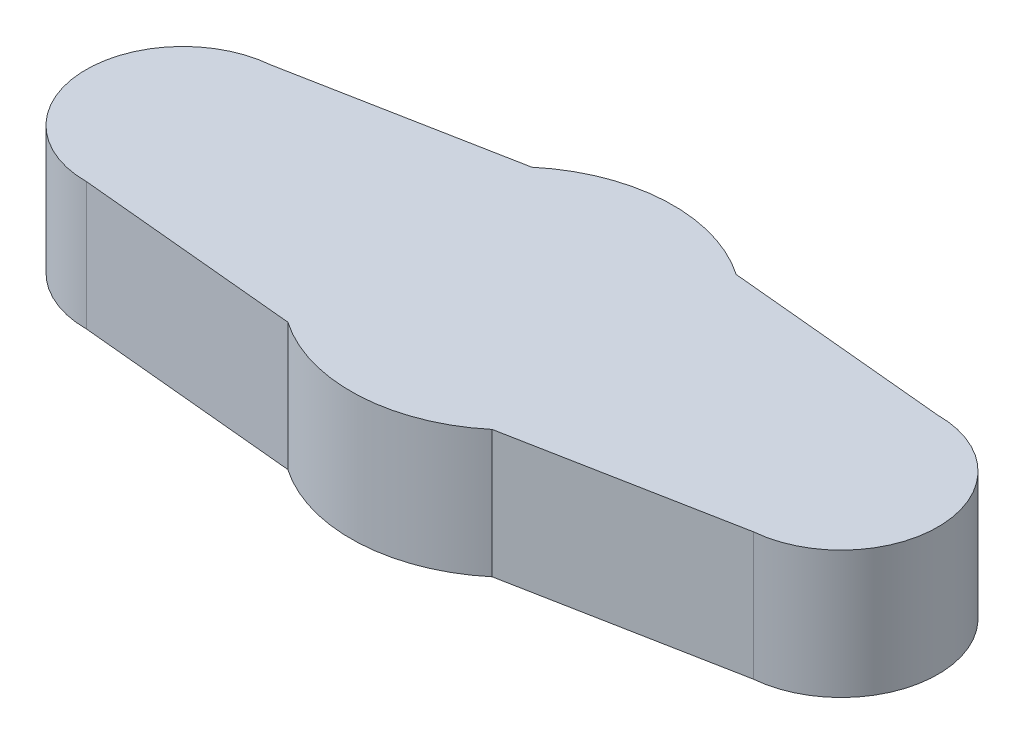
SolidWorks part; units mm, degrees
ref_plane "Front Plane" through (0, 0, 0) normal (0, 0, 1) x (1, 0, 0)
ref_plane "Top Plane" through (0, 0, 0) normal (0, 1, 0) x (1, 0, 0)
ref_plane "Right Plane" through (0, 0, 0) normal (1, 0, 0) x (0, 0, -1)
sketch "Sketch1" plane through (0, 19.05, 0) normal (0, 1, 0) x (1, 0, 0)
  line L8 (7.1827, 4.1213) -> (-5.1818, 1.7547)
  line L9 (-4.9411, -3.3196) -> (7.592, -4.505)
  line L10 (15.6773, -4.1213) -> (28.0418, -1.7547)
  line L11 (27.8011, 3.3196) -> (15.268, 4.505)
  line L12 (7.1827, 4.1213) -> (-5.1818, 1.7547)
  line L13 (-4.9411, -3.3196) -> (7.592, -4.505)
  line L14 (15.6773, -4.1213) -> (28.0418, -1.7547)
  line L15 (27.8011, 3.3196) -> (15.268, 4.505)
  line L20 (27.8917, 5.8624) -> (16.2283, 6.9655)
  line L21 (16.8662, -6.4799) -> (28.3728, -4.2775)
  line L22 (-5.0317, -5.8624) -> (6.6317, -6.9655)
  line L23 (5.9938, 6.4799) -> (-5.5128, 4.2775)
  line L24 (27.8917, 5.8624) -> (16.2283, 6.9655)
  line L25 (16.8662, -6.4799) -> (28.3728, -4.2775)
  line L26 (-5.0317, -5.8624) -> (6.6317, -6.9655)
  line L27 (5.9938, 6.4799) -> (-5.5128, 4.2775)
  circle A0 centre (11.43, 0) radius 2.032
  arc A9 (15.268, 4.505) -> (7.1827, 4.1213) centre (11.43, 0) ccw
  arc A10 (-5.1818, 1.7547) -> (-4.9411, -3.3196) centre (-5.0614, -0.7825) ccw
  arc A11 (7.592, -4.505) -> (15.6773, -4.1213) centre (11.43, 0) ccw
  arc A12 (28.0418, -1.7547) -> (27.8011, 3.3196) centre (27.9214, 0.7825) ccw
  arc A13 (15.268, 4.505) -> (7.1827, 4.1213) centre (11.43, 0) ccw
  arc A14 (-5.1818, 1.7547) -> (-4.9411, -3.3196) centre (-5.0614, -0.7825) ccw
  arc A15 (7.592, -4.505) -> (15.6773, -4.1213) centre (11.43, 0) ccw
  arc A16 (28.0418, -1.7547) -> (27.8011, 3.3196) centre (27.9214, 0.7825) ccw
  arc A21 (16.2283, 6.9655) -> (5.9938, 6.4799) centre (11.43, 0) ccw
  arc A22 (28.3728, -4.2775) -> (27.8917, 5.8624) centre (27.9214, 0.7825) ccw
  arc A23 (6.6317, -6.9655) -> (16.8662, -6.4799) centre (11.43, 0) ccw
  arc A24 (-5.5128, 4.2775) -> (-5.0317, -5.8624) centre (-5.0614, -0.7825) ccw
  arc A25 (16.2283, 6.9655) -> (5.9938, 6.4799) centre (11.43, 0) ccw
  arc A26 (28.3728, -4.2775) -> (27.8917, 5.8624) centre (27.9214, 0.7825) ccw
  arc A27 (6.6317, -6.9655) -> (16.8662, -6.4799) centre (11.43, 0) ccw
  arc A28 (-5.5128, 4.2775) -> (-5.0317, -5.8624) centre (-5.0614, -0.7825) ccw
  point P3 (0, 0)
  arc M2 (15.268, 4.505) -> (7.1827, 4.1213) centre (11.43, 0) ccw
  line M3 (7.1827, 4.1213) -> (-5.1818, 1.7547)
  arc M4 (-5.1818, 1.7547) -> (-4.9411, -3.3196) centre (-5.0614, -0.7825) ccw
  line M5 (-4.9411, -3.3196) -> (7.592, -4.505)
  arc M6 (7.592, -4.505) -> (15.6773, -4.1213) centre (11.43, 0) ccw
  line M7 (15.6773, -4.1213) -> (28.0418, -1.7547)
  arc M8 (28.0418, -1.7547) -> (27.8011, 3.3196) centre (27.9214, 0.7825) ccw
  line M9 (27.8011, 3.3196) -> (15.268, 4.505)
  dimension "D1" = 4.064
  dimension "D2" = 0
  dimension "D3" = 2.54
extrude "Boss-Extrude1" add sketch "Sketch1" along normal blind 2.159 contours L27 A28 L26 A27 L25 A26 L24 A25 A16 L14 A15 L13 A14 L12 A13 L15 | A0 M9 M2 M3 M4 M5 M6 M7 M8 | L14 A16 L15 A13 L12 A14 L13 A15 M2 M9 M8 M7 M6 M5 M4 M3 region at (11.1684, 19.05, -5.5134) region at (32.5329, 19.05, -1.0013)
extrude "Boss-Extrude2" add sketch "Sketch1<3>" against normal up to surface (2.54 mm away) contours L27 A28 L26 A27 L25 A26 L24 A25 A16 L14 A15 L13 A14 L12 A13 L15 region at (32.5329, 19.05, -1.0013)
sketch "Sketch1<3>" plane through (0, 19.05, 0) normal (0, 1, 0) x (1, 0, 0) same geometry as "Sketch1"
extrude "Boss-Extrude3" add sketch "Sketch1<4>" along normal blind 2 from surface contours A27 L25 A26 L24 A25 L27 A28 L26 starting at face at (11.43, 21.209, 0)
sketch "Sketch1<4>" plane through (0, 19.05, 0) normal (0, 1, 0) x (1, 0, 0) same geometry as "Sketch1"
